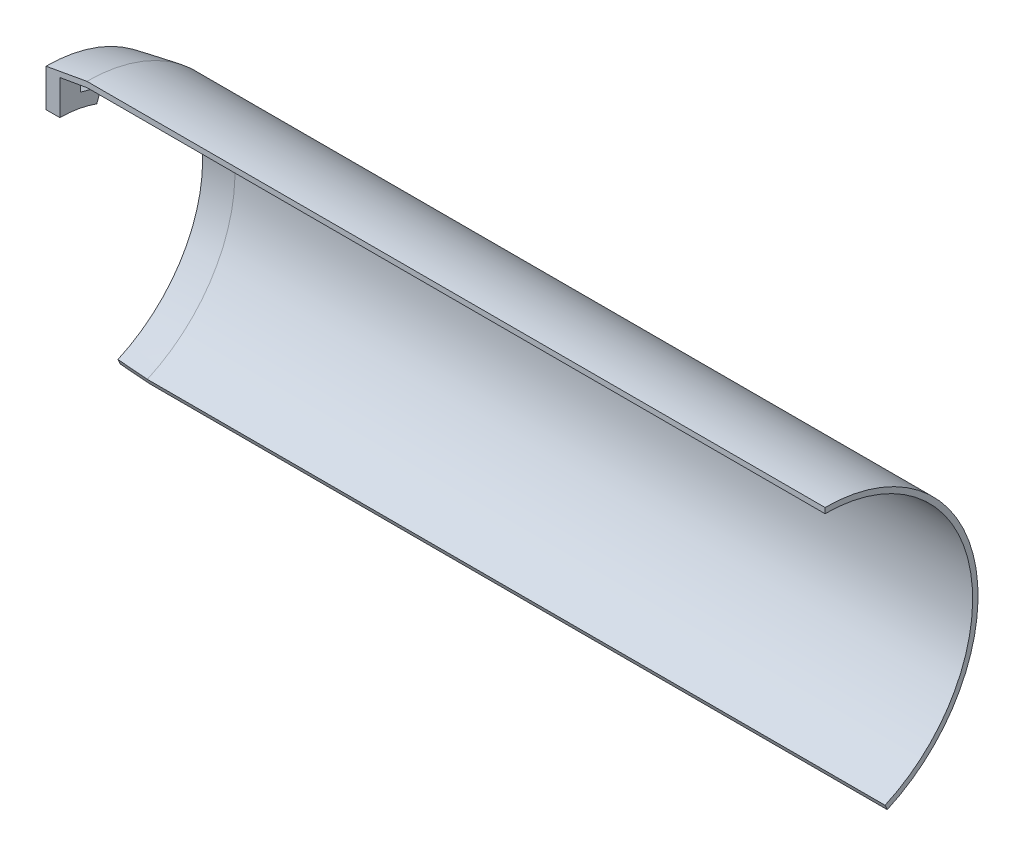
SolidWorks part; units mm, degrees
ref_plane "Front Plane" through (0, 0, 0) normal (0, 0, 1) x (1, 0, 0)
ref_plane "Top Plane" through (0, 0, 0) normal (0, 1, 0) x (1, 0, 0)
ref_plane "Right Plane" through (0, 0, 0) normal (1, 0, 0) x (0, 0, -1)
curve "Curve1"
  spline degree 3 poles (0, 0, 0) (-0.0123, 3.8916, 0) (-0.0274, 8.685, 0) (0.3616, 14.0857, 0) (0.5761, 16.0905, 0) (0.7825, 17.6048, 0) (0.9862, 18.8543, 0) (1.1887, 19.9315, 0) (1.3904, 20.8857, 0) (1.5917, 21.7465, 0) (1.7927, 22.5337, 0) (1.9935, 23.2611, 0) (2.1942, 23.9386, 0) (2.3947, 24.5739, 0) (2.5952, 25.1728, 0) (2.7956, 25.7401, 0) (2.9959, 26.2796, 0) (3.1962, 26.7943, 0) (3.3965, 27.2868, 0) (3.5967, 27.7594, 0) (3.7969, 28.2139, 0) (3.9971, 28.6519, 0) (4.1973, 29.0748, 0) (4.3974, 29.4838, 0) (4.5976, 29.8799, 0) (4.7977, 30.2641, 0) (4.9978, 30.6373, 0) (5.1979, 31.0001, 0) (5.398, 31.3533, 0) (5.5981, 31.6974, 0) (5.7982, 32.033, 0) (5.9983, 32.3606, 0) (6.1984, 32.6807, 0) (6.3985, 32.9935, 0) (6.5985, 33.2996, 0) (6.7986, 33.5993, 0) (6.9986, 33.8929, 0) (7.1987, 34.1806, 0) (7.3987, 34.4628, 0) (7.5988, 34.7397, 0) (7.7988, 35.0115, 0) (7.9989, 35.2785, 0) (8.1989, 35.5408, 0) (8.399, 35.7988, 0) (8.599, 36.0524, 0) (8.799, 36.3019, 0) (8.9991, 36.5476, 0) (9.1991, 36.7894, 0) (9.3991, 37.0275, 0) (9.5992, 37.2622, 0) (9.7992, 37.4934, 0) (9.9992, 37.7214, 0) (10.1992, 37.9461, 0) (10.3993, 38.1679, 0) (10.5993, 38.3866, 0) (10.7993, 38.6025, 0) (10.9993, 38.8156, 0) (11.1993, 39.026, 0) (11.3994, 39.2338, 0) (11.5994, 39.4391, 0) (11.7994, 39.6419, 0) (11.9994, 39.8422, 0) (12.1994, 40.0403, 0) (12.3995, 40.2361, 0) (12.5995, 40.4297, 0) (12.7995, 40.6212, 0) (12.9995, 40.8106, 0) (13.1995, 40.998, 0) (13.3995, 41.1834, 0) (13.5995, 41.3668, 0) (13.7995, 41.5484, 0) (13.9996, 41.7281, 0) (14.1996, 41.9061, 0) (14.3996, 42.0823, 0) (14.5996, 42.2568, 0) (14.7996, 42.4296, 0) (14.9996, 42.6008, 0) (15.1996, 42.7705, 0) (15.3996, 42.9385, 0) (15.5996, 43.1051, 0) (15.7996, 43.2701, 0) (15.9997, 43.4337, 0) (16.1997, 43.5959, 0) (16.3997, 43.7567, 0) (16.5997, 43.9161, 0) (16.7997, 44.0742, 0) (16.9997, 44.2309, 0) (17.1997, 44.3864, 0) (17.3997, 44.5406, 0) (17.5997, 44.6936, 0) (17.7997, 44.8453, 0) (17.9997, 44.9959, 0) (18.1997, 45.1453, 0) (18.3997, 45.2936, 0) (18.5997, 45.4407, 0) (18.7997, 45.5868, 0) (18.9997, 45.7317, 0) (19.1998, 45.8756, 0) (19.3998, 46.0185, 0) (19.5998, 46.1603, 0) (19.7998, 46.3011, 0) (19.9998, 46.4409, 0) (20.1998, 46.5797, 0) (20.3998, 46.7176, 0) (20.5998, 46.8546, 0) (20.7998, 46.9906, 0) (20.9998, 47.1257, 0) (21.1998, 47.2599, 0) (21.3998, 47.3932, 0) (21.5998, 47.5256, 0) (21.7998, 47.6572, 0) (21.9998, 47.788, 0) (22.1998, 47.9179, 0) (22.3998, 48.047, 0) (22.5998, 48.1753, 0) (22.7998, 48.3028, 0) (22.9998, 48.4295, 0) (23.1998, 48.5555, 0) (23.3998, 48.6807, 0) (23.5998, 48.8051, 0) (23.7998, 48.9288, 0) (23.9998, 49.0518, 0) (24.1998, 49.1741, 0) (24.3998, 49.2957, 0) (24.5998, 49.4165, 0) (24.7999, 49.5367, 0) (24.9999, 49.6562, 0) (25.1999, 49.7751, 0) (25.3999, 49.8933, 0) (25.5999, 50.0108, 0) (25.7999, 50.1277, 0) (25.9999, 50.2439, 0) (26.1999, 50.3596, 0) (26.3999, 50.4746, 0) (26.5999, 50.589, 0) (26.7999, 50.7028, 0) (26.9999, 50.8161, 0) (27.1999, 50.9287, 0) (27.3999, 51.0407, 0) (27.5999, 51.1522, 0) (27.7999, 51.2631, 0) (27.9999, 51.3735, 0) (28.1999, 51.4833, 0) (28.3999, 51.5926, 0) (28.5999, 51.7013, 0) (28.7999, 51.8095, 0) (28.9999, 51.9172, 0) (29.1999, 52.0243, 0) (29.3999, 52.131, 0) (29.5999, 52.2371, 0) (29.7999, 52.3428, 0) (29.9999, 52.4479, 0) (30.1999, 52.5526, 0) (30.3999, 52.6567, 0) (30.5999, 52.7604, 0) (30.7999, 52.8636, 0) (30.9999, 52.9664, 0) (31.1999, 53.0687, 0) (31.3999, 53.1705, 0) (31.5999, 53.2719, 0) (31.7999, 53.3728, 0) (31.9999, 53.4733, 0) (32.1999, 53.5733, 0) (32.3999, 53.6729, 0) (32.5999, 53.7721, 0) (32.7999, 53.8709, 0) (32.9999, 53.9692, 0) (33.1999, 54.0671, 0) (33.3999, 54.1646, 0) (33.5999, 54.2617, 0) (33.7999, 54.3584, 0) (33.9999, 54.4547, 0) (34.1999, 54.5506, 0) (34.3999, 54.6461, 0) (34.5999, 54.7412, 0) (34.7999, 54.836, 0) (34.9999, 54.9303, 0) (35.1999, 55.0243, 0) (35.3999, 55.1179, 0) (35.5999, 55.2111, 0) (35.7999, 55.304, 0) (35.9999, 55.3965, 0) (36.1999, 55.4887, 0) (36.3999, 55.5805, 0) (36.5999, 55.6719, 0) (36.7999, 55.763, 0) (36.9999, 55.8537, 0) (37.1999, 55.9441, 0) (37.3999, 56.0342, 0) (37.5999, 56.1239, 0) (37.7999, 56.2133, 0) (37.9999, 56.3024, 0) (38.1999, 56.3911, 0) (38.3999, 56.4795, 0) (38.5999, 56.5676, 0) (38.7999, 56.6554, 0) (38.9999, 56.7428, 0) (39.1999, 56.83, 0) (39.3999, 56.9168, 0) (39.5999, 57.0033, 0) (39.7999, 57.0896, 0) (39.9999, 57.1755, 0) (40.1999, 57.2611, 0) (40.3999, 57.3464, 0) (40.5999, 57.4314, 0) (40.7999, 57.5161, 0) (40.9999, 57.6006, 0) (41.1999, 57.6847, 0) (41.3999, 57.7686, 0) (41.6, 57.8522, 0) (41.8, 57.9355, 0) (42, 58.0185, 0) (42.2, 58.1012, 0) (42.4, 58.1837, 0) (42.6, 58.2659, 0) (42.8, 58.3479, 0) (43, 58.4295, 0) (43.2, 58.5109, 0) (43.4, 58.592, 0) (43.6, 58.6729, 0) (43.8, 58.7535, 0) (44, 58.8339, 0) (44.2, 58.914, 0) (44.4, 58.9938, 0) (44.6, 59.0734, 0) (44.8, 59.1528, 0) (45, 59.2319, 0) (45.2, 59.3107, 0) (45.4, 59.3893, 0) (45.6, 59.4677, 0) (45.8, 59.5458, 0) (46, 59.6237, 0) (46.2, 59.7014, 0) (46.4, 59.7788, 0) (46.6, 59.856, 0) (46.8, 59.9329, 0) (47, 60.0096, 0) (47.2, 60.0861, 0) (47.4, 60.1624, 0) (47.6, 60.2385, 0) (47.8, 60.3143, 0) (48, 60.3899, 0) (48.2, 60.4652, 0) (48.4, 60.5404, 0) (48.6, 60.6153, 0) (48.8, 60.6901, 0) (49, 60.7646, 0) (49.2, 60.8389, 0) (49.4, 60.913, 0) (49.6, 60.9869, 0) (49.8, 61.0605, 0) (50, 61.134, 0) (50.2, 61.2072, 0) (50.4, 61.2803, 0) (50.6, 61.3531, 0) (50.8, 61.4258, 0) (51, 61.4982, 0) (51.2, 61.5705, 0) (51.4, 61.6426, 0) (51.6, 61.7144, 0) (51.8, 61.7861, 0) (52, 61.8575, 0) (52.2, 61.9288, 0) (52.4, 61.9999, 0) (52.6, 62.0708, 0) (52.8, 62.1415, 0) (53, 62.212, 0) (53.2, 62.2824, 0) (53.4, 62.3525, 0) (53.6, 62.4225, 0) (53.8, 62.4923, 0) (54, 62.5619, 0) (54.2, 62.6313, 0) (54.4, 62.7006, 0) (54.6, 62.7696, 0) (54.8, 62.8385, 0) (55, 62.9072, 0) (55.2, 62.9758, 0) (55.4, 63.0441, 0) (55.6, 63.1123, 0) (55.8, 63.1803, 0) (56, 63.2482, 0) (56.2, 63.3159, 0) (56.4, 63.3834, 0) (56.6, 63.4507, 0) (56.8, 63.5179, 0) (57, 63.5849, 0) (57.2, 63.6518, 0) (57.4, 63.7185, 0) (57.6, 63.785, 0) (57.8, 63.8513, 0) (58, 63.9175, 0) (58.2, 63.9836, 0) (58.4, 64.0495, 0) (58.6, 64.1152, 0) (58.8, 64.1808, 0) (59, 64.2462, 0) (59.2, 64.3114, 0) (59.4, 64.3765, 0) (59.6, 64.4415, 0) (59.8, 64.5063, 0) (60, 64.5709, 0) (60.2, 64.6354, 0) (60.4, 64.6998, 0) (60.6, 64.764, 0) (60.8, 64.828, 0) (61, 64.8919, 0) (61.2, 64.9557, 0) (61.4, 65.0193, 0) (61.6, 65.0827, 0) (61.8, 65.1461, 0) (62, 65.2092, 0) (62.2, 65.2723, 0) (62.4, 65.3352, 0) (62.6, 65.3979, 0) (62.8, 65.4605, 0) (63, 65.523, 0) (63.2, 65.5853, 0) (63.4, 65.6475, 0) (63.6, 65.7096, 0) (63.8, 65.7715, 0) (64, 65.8333, 0) (64.2, 65.895, 0) (64.4, 65.9565, 0) (64.6, 66.0179, 0) (64.8, 66.0791, 0) (65, 66.1402, 0) (65.2, 66.2012, 0) (65.4, 66.2621, 0) (65.6, 66.3228, 0) (65.8, 66.3834, 0) (66, 66.4439, 0) (66.2, 66.5042, 0) (66.4, 66.5644, 0) (66.6, 66.6245, 0) (66.8, 66.6845, 0) (67, 66.7443, 0) (67.2, 66.804, 0) (67.4, 66.8636, 0) (67.6, 66.923, 0) (67.8, 66.9824, 0) (68, 67.0416, 0) (68.2, 67.1007, 0) (68.4, 67.1597, 0) (68.6, 67.2185, 0) (68.8, 67.2772, 0) (69, 67.3359, 0) (69.2, 67.3943, 0) (69.4, 67.4527, 0) (69.6, 67.511, 0) (69.8, 67.5691, 0) (70, 67.6271, 0) (70.2, 67.6851, 0) (70.4, 67.7428, 0) (70.6, 67.8005, 0) (70.8, 67.8581, 0) (71, 67.9155, 0) (71.2, 67.9729, 0) (71.4, 68.0301, 0) (71.6, 68.0872, 0) (71.8, 68.1442, 0) (72, 68.2011, 0) (72.2, 68.2579, 0) (72.4, 68.3145, 0) (72.6, 68.3711, 0) (72.8, 68.4276, 0) (73, 68.4839, 0) (73.2, 68.5401, 0) (73.4, 68.5963, 0) (73.6, 68.6523, 0) (73.8, 68.7082, 0) (74, 68.764, 0) (74.2, 68.8197, 0) (74.4, 68.8753, 0) (74.6, 68.9308, 0) (74.8, 68.9862, 0) (75, 69.0415, 0) (75.2, 69.0966, 0) (75.4, 69.1517, 0) (75.6, 69.2067, 0) (75.8, 69.2616, 0) (76, 69.3164, 0) (76.2, 69.371, 0) (76.4, 69.4256, 0) (76.6, 69.4801, 0) (76.8, 69.5344, 0) (77, 69.5887, 0) (77.2, 69.6429, 0) (77.4, 69.697, 0) (77.6, 69.751, 0) (77.8, 69.8048, 0) (78, 69.8586, 0) (78.2, 69.9123, 0) (78.4, 69.9659, 0) (78.6, 70.0194, 0) (78.8, 70.0728, 0) (79, 70.1261, 0) (79.2, 70.1793, 0) (79.4, 70.2324, 0) (79.6, 70.2855, 0) (79.8, 70.3384, 0) (80, 70.3912, 0) (80.2, 70.444, 0) (80.4, 70.4966, 0) (80.6, 70.5492, 0) (80.8, 70.6017, 0) (81, 70.6541, 0) (81.2, 70.7064, 0) (81.4, 70.7586, 0) (81.6, 70.8107, 0) (81.8, 70.8627, 0) (82, 70.9146, 0) (82.2, 70.9665, 0) (82.4, 71.0182, 0) (82.6, 71.0699, 0) (82.8, 71.1215, 0) (83, 71.173, 0) (83.2, 71.2244, 0) (83.4, 71.2757, 0) (83.6, 71.3269, 0) (83.8, 71.3781, 0) (84, 71.4291, 0) (84.2, 71.4801, 0) (84.4, 71.531, 0) (84.6, 71.5818, 0) (84.8, 71.6325, 0) (85, 71.6832, 0) (85.2, 71.7337, 0) (85.4, 71.7842, 0) (85.6, 71.8346, 0) (85.8, 71.8849, 0) (86, 71.9351, 0) (86.2, 71.9853, 0) (86.4, 72.0354, 0) (86.6, 72.0853, 0) (86.8, 72.1352, 0) (87, 72.1851, 0) (87.2, 72.2348, 0) (87.4, 72.2845, 0) (87.6, 72.3341, 0) (87.8, 72.3836, 0) (88, 72.433, 0) (88.2, 72.4823, 0) (88.4, 72.5316, 0) (88.6, 72.5808, 0) (88.8, 72.6299, 0) (89, 72.6789, 0) (89.2, 72.7279, 0) (89.4, 72.7768, 0) (89.6, 72.8256, 0) (89.8, 72.8743, 0) (90, 72.923, 0) (90.2, 72.9716, 0) (90.4, 73.0201, 0) (90.6, 73.0685, 0) (90.8, 73.1168, 0) (91, 73.1651, 0) (91.2, 73.2133, 0) (91.4, 73.2614, 0) (91.6, 73.3095, 0) (91.8, 73.3575, 0) (92, 73.4054, 0) (92.2, 73.4532, 0) (92.4, 73.501, 0) (92.6, 73.5487, 0) (92.8, 73.5963, 0) (93, 73.6439, 0) (93.2, 73.6913, 0) (93.4, 73.7387, 0) (93.6, 73.7861, 0) (93.8, 73.8333, 0) (94, 73.8805, 0) (94.2, 73.9276, 0) (94.4, 73.9747, 0) (94.6, 74.0217, 0) (94.8, 74.0686, 0) (95, 74.1154, 0) (95.2, 74.1622, 0) (95.4, 74.2089, 0) (95.6, 74.2556, 0) (95.8, 74.3021, 0) (96, 74.3486, 0) (96.2, 74.3951, 0) (96.4, 74.4414, 0) (96.6, 74.4877, 0) (96.8, 74.534, 0) (97, 74.5801, 0) (97.2, 74.6262, 0) (97.4, 74.6723, 0) (97.6, 74.7182, 0) (97.8, 74.7641, 0) (98, 74.81, 0) (98.2, 74.8557, 0) (98.4, 74.9014, 0) (98.6, 74.9471, 0) (98.8, 74.9926, 0) (99, 75.0382, 0) (99.2, 75.0836, 0) (99.4, 75.129, 0) (99.6, 75.1743, 0) (99.8, 75.2196, 0) (100, 75.2647, 0) (100.2, 75.3099, 0) (100.4, 75.3549, 0) (100.6, 75.3999, 0) (100.8, 75.4449, 0) (101, 75.4898, 0) (101.2, 75.5346, 0) (101.4, 75.5793, 0) (101.6, 75.624, 0) (101.8, 75.6686, 0) (102, 75.7132, 0) (102.2, 75.7577, 0) (102.4, 75.8022, 0) (102.6, 75.8465, 0) (102.8, 75.8909, 0) (103, 75.9351, 0) (103.2, 75.9793, 0) (103.4, 76.0235, 0) (103.6, 76.0676, 0) (103.8, 76.1116, 0) (104, 76.1556, 0) (104.2, 76.1995, 0) (104.4, 76.2433, 0) (104.6, 76.2871, 0) (104.8, 76.3308, 0) (105, 76.3745, 0) (105.2, 76.4181, 0) (105.4, 76.4617, 0) (105.6, 76.5052, 0) (105.8, 76.5486, 0) (106, 76.592, 0) (106.2, 76.6353, 0) (106.4, 76.6786, 0) (106.6, 76.7218, 0) (106.8, 76.7649, 0) (107, 76.808, 0) (107.2, 76.8511, 0) (107.4, 76.8941, 0) (107.6, 76.937, 0) (107.8, 76.9799, 0) (108, 77.0227, 0) (108.2, 77.0655, 0) (108.4, 77.1082, 0) (108.6, 77.1508, 0) (108.8, 77.1934, 0) (109, 77.236, 0) (109.2, 77.2784, 0) (109.4, 77.3209, 0) (109.6, 77.3633, 0) (109.8, 77.4056, 0) (110, 77.4479, 0) (110.2, 77.4901, 0) (110.4, 77.5322, 0) (110.6, 77.5743, 0) (110.8, 77.6164, 0) (111, 77.6584, 0) (111.2, 77.7004, 0) (111.4, 77.7423, 0) (111.6, 77.7841, 0) (111.8, 77.8259, 0) (112, 77.8676, 0) (112.2, 77.9093, 0) (112.4, 77.951, 0) (112.6, 77.9925, 0) (112.8, 78.0341, 0) (113, 78.0756, 0) (113.2, 78.117, 0) (113.4, 78.1584, 0) (113.6, 78.1997, 0) (113.8, 78.241, 0) (114, 78.2822, 0) (114.2, 78.3234, 0) (114.4, 78.3645, 0) (114.6, 78.4056, 0) (114.8, 78.4466, 0) (115, 78.4876, 0) (115.2, 78.5285, 0) (115.4, 78.5694, 0) (115.6, 78.6102, 0) (115.8, 78.651, 0) (116, 78.6917, 0) (116.2, 78.7324, 0) (116.4, 78.773, 0) (116.6, 78.8136, 0) (116.8, 78.8541, 0) (117, 78.8946, 0) (117.2, 78.935, 0) (117.4, 78.9754, 0) (117.6, 79.0158, 0) (117.8, 79.0561, 0) (118, 79.0963, 0) (118.2, 79.1365, 0) (118.4, 79.1766, 0) (118.6, 79.2167, 0) (118.8, 79.2568, 0) (119, 79.2968, 0) (119.2, 79.3368, 0) (119.4, 79.3767, 0) (119.6, 79.4165, 0) (119.8, 79.4564, 0) (120, 79.4961, 0) (120.2, 79.5358, 0) (120.4, 79.5755, 0) (120.6, 79.6152, 0) (120.8, 79.6547, 0) (121, 79.6943, 0) (121.2, 79.7338, 0) (121.4, 79.7732, 0) (121.6, 79.8126, 0) (121.8, 79.852, 0) (122, 79.8913, 0) (122.2, 79.9306, 0) (122.4, 79.9698, 0) (122.6, 80.009, 0) (122.8, 80.0481, 0) (123, 80.0872, 0) (123.2, 80.1262, 0) (123.4, 80.1652, 0) (123.6, 80.2042, 0) (123.8, 80.2431, 0) (124, 80.282, 0) (124.2, 80.3208, 0) (124.4, 80.3596, 0) (124.6, 80.3983, 0) (124.8, 80.437, 0) (125, 80.4757, 0) (125.2, 80.5143, 0) (125.4, 80.5528, 0) (125.6, 80.5914, 0) (125.8, 80.6298, 0) (126, 80.6683, 0) (126.2, 80.7067, 0) (126.4, 80.745, 0) (126.6, 80.7833, 0) (126.8, 80.8216, 0) (127, 80.8598, 0) (127.2, 80.898, 0) (127.4, 80.9361, 0) (127.6, 80.9742, 0) (127.8, 81.0123, 0) (128, 81.0503, 0) (128.2, 81.0883, 0) (128.4, 81.1262, 0) (128.6, 81.1641, 0) (128.8, 81.2019, 0) (129, 81.2397, 0) (129.2, 81.2775, 0) (129.4, 81.3152, 0) (129.6, 81.3529, 0) (129.8, 81.3906, 0) (130, 81.4282, 0) (130.2, 81.4657, 0) (130.4, 81.5032, 0) (130.6, 81.5407, 0) (130.8, 81.5782, 0) (131, 81.6156, 0) (131.2, 81.6529, 0) (131.4, 81.6902, 0) (131.6, 81.7275, 0) (131.8, 81.7648, 0) (132, 81.802, 0) (132.2, 81.8391, 0) (132.4, 81.8763, 0) (132.6, 81.9133, 0) (132.8, 81.9504, 0) (133, 81.9874, 0) (133.2, 82.0244, 0) (133.4, 82.0613, 0) (133.6, 82.0982, 0) (133.8, 82.135, 0) (134, 82.1718, 0) (134.2, 82.2086, 0) (134.4, 82.2454, 0) (134.6, 82.282, 0) (134.8, 82.3187, 0) (135, 82.3553, 0) (135.2, 82.3919, 0) (135.4, 82.4285, 0) (135.6, 82.465, 0) (135.8, 82.5014, 0) (136, 82.5379, 0) (136.2, 82.5743, 0) (136.4, 82.6106, 0) (136.6, 82.6469, 0) (136.8, 82.6832, 0) (137, 82.7195, 0) (137.2, 82.7557, 0) (137.4, 82.7919, 0) (137.6, 82.828, 0) (137.8, 82.8641, 0) (138, 82.9001, 0) (138.2, 82.9362, 0) (138.4, 82.9722, 0) (138.6, 83.0081, 0) (138.8, 83.044, 0) (139, 83.0799, 0) (139.2, 83.1158, 0) (139.4, 83.1516, 0) (139.6, 83.1873, 0) (139.8, 83.2231, 0) (140, 83.2588, 0) (140.2, 83.2944, 0) (140.4, 83.3301, 0) (140.6, 83.3657, 0) (140.8, 83.4012, 0) (141, 83.4367, 0) (141.2, 83.4722, 0) (141.4, 83.5077, 0) (141.6, 83.5431, 0) (141.8, 83.5785, 0) (142, 83.6138, 0) (142.2, 83.6491, 0) (142.4, 83.6844, 0) (142.6, 83.7197, 0) (142.8, 83.7549, 0) (143, 83.79, 0) (143.2, 83.8252, 0) (143.4, 83.8603, 0) (143.6, 83.8954, 0) (143.8, 83.9304, 0) (144, 83.9654, 0) (144.2, 84.0004, 0) (144.4, 84.0353, 0) (144.6, 84.0702, 0) (144.8, 84.1051, 0) (145, 84.1399, 0) (145.2, 84.1747, 0) (145.4, 84.2095, 0) (145.6, 84.2442, 0) (145.8, 84.2789, 0) (146, 84.3136, 0) (146.2, 84.3482, 0) (146.4, 84.3828, 0) (146.6, 84.4174, 0) (146.8, 84.4519, 0) (147, 84.4864, 0) (147.2, 84.5209, 0) (147.4, 84.5553, 0) (147.6, 84.5897, 0) (147.8, 84.6241, 0) (148, 84.6584, 0) (148.2, 84.6927, 0) (148.4, 84.727, 0) (148.6, 84.7612, 0) (148.8, 84.7954, 0) (149, 84.8296, 0) (149.2, 84.8638, 0) (149.4, 84.8979, 0) (149.6, 84.9319, 0) (149.8, 84.966, 0) (149.9333, 84.9887, 0) (150, 85, 0) knots 0 0 0 0 0.061462 0.075706 0.085548 0.093322 0.099856 0.105554 0.110643 0.115268 0.119525 0.123482 0.127192 0.130691 0.13401 0.137173 0.140199 0.143104 0.145901 0.148602 0.151215 0.15375 0.156213 0.158609 0.160946 0.163227 0.165456 0.167638 0.169775 0.171871 0.173928 0.17595 0.177937 0.179893 0.181819 0.183716 0.185587 0.187433 0.189255 0.191054 0.192831 0.194589 0.196326 0.198045 0.199747 0.201431 0.2031 0.204753 0.206391 0.208015 0.209626 0.211223 0.212808 0.214381 0.215942 0.217493 0.219032 0.220561 0.22208 0.22359 0.225091 0.226582 0.228065 0.229539 0.231006 0.232464 0.233915 0.235359 0.236795 0.238225 0.239648 0.241065 0.242475 0.243879 0.245277 0.24667 0.248057 0.249438 0.250814 0.252185 0.253551 0.254913 0.256269 0.257621 0.258968 0.260311 0.26165 0.262984 0.264315 0.265641 0.266964 0.268282 0.269598 0.270909 0.272217 0.273522 0.274823 0.276121 0.277416 0.278707 0.279996 0.281281 0.282564 0.283843 0.28512 0.286394 0.287666 0.288935 0.290201 0.291465 0.292726 0.293985 0.295241 0.296495 0.297747 0.298996 0.300243 0.301489 0.302732 0.303972 0.305211 0.306448 0.307683 0.308916 0.310147 0.311376 0.312604 0.313829 0.315053 0.316275 0.317495 0.318714 0.319931 0.321147 0.32236 0.323573 0.324783 0.325993 0.3272 0.328406 0.329611 0.330815 0.332017 0.333217 0.334416 0.335614 0.336811 0.338006 0.3392 0.340393 0.341584 0.342775 0.343964 0.345152 0.346339 0.347524 0.348709 0.349892 0.351074 0.352256 0.353436 0.354615 0.355793 0.35697 0.358146 0.359321 0.360495 0.361668 0.36284 0.364011 0.365182 0.366351 0.36752 0.368687 0.369854 0.37102 0.372185 0.373349 0.374512 0.375674 0.376836 0.377997 0.379157 0.380316 0.381475 0.382632 0.383789 0.384946 0.386101 0.387256 0.38841 0.389563 0.390716 0.391868 0.393019 0.39417 0.39532 0.396469 0.397618 0.398766 0.399913 0.40106 0.402206 0.403351 0.404496 0.40564 0.406784 0.407927 0.409069 0.410211 0.411353 0.412493 0.413633 0.414773 0.415912 0.417051 0.418189 0.419326 0.420463 0.4216 0.422736 0.423871 0.425006 0.426141 0.427275 0.428408 0.429541 0.430674 0.431806 0.432937 0.434068 0.435199 0.436329 0.437459 0.438588 0.439717 0.440846 0.441974 0.443101 0.444229 0.445355 0.446482 0.447608 0.448733 0.449858 0.450983 0.452107 0.453231 0.454355 0.455478 0.456601 0.457723 0.458845 0.459967 0.461088 0.462209 0.46333 0.46445 0.46557 0.46669 0.467809 0.468928 0.470046 0.471164 0.472282 0.4734 0.474517 0.475634 0.47675 0.477866 0.478982 0.480098 0.481213 0.482328 0.483443 0.484557 0.485671 0.486785 0.487898 0.489011 0.490124 0.491237 0.492349 0.493461 0.494573 0.495684 0.496796 0.497906 0.499017 0.500127 0.501237 0.502347 0.503457 0.504566 0.505675 0.506784 0.507892 0.509001 0.510109 0.511216 0.512324 0.513431 0.514538 0.515645 0.516752 0.517858 0.518964 0.52007 0.521175 0.522281 0.523386 0.524491 0.525595 0.5267 0.527804 0.528908 0.530012 0.531116 0.532219 0.533322 0.534425 0.535528 0.53663 0.537733 0.538835 0.539937 0.541038 0.54214 0.543241 0.544342 0.545443 0.546544 0.547644 0.548745 0.549845 0.550945 0.552044 0.553144 0.554243 0.555342 0.556441 0.55754 0.558639 0.559737 0.560836 0.561934 0.563032 0.564129 0.565227 0.566324 0.567421 0.568518 0.569615 0.570712 0.571809 0.572905 0.574001 0.575097 0.576193 0.577289 0.578384 0.57948 0.580575 0.58167 0.582765 0.58386 0.584954 0.586049 0.587143 0.588237 0.589331 0.590425 0.591519 0.592612 0.593706 0.594799 0.595892 0.596985 0.598078 0.59917 0.600263 0.601355 0.602448 0.60354 0.604632 0.605724 0.606815 0.607907 0.608998 0.61009 0.611181 0.612272 0.613363 0.614453 0.615544 0.616635 0.617725 0.618815 0.619905 0.620995 0.622085 0.623175 0.624265 0.625354 0.626443 0.627533 0.628622 0.629711 0.6308 0.631888 0.632977 0.634066 0.635154 0.636242 0.637331 0.638419 0.639507 0.640594 0.641682 0.64277 0.643857 0.644945 0.646032 0.647119 0.648206 0.649293 0.65038 0.651467 0.652553 0.65364 0.654726 0.655813 0.656899 0.657985 0.659071 0.660157 0.661243 0.662328 0.663414 0.664499 0.665585 0.66667 0.667755 0.66884 0.669925 0.67101 0.672095 0.67318 0.674264 0.675349 0.676433 0.677518 0.678602 0.679686 0.68077 0.681854 0.682938 0.684022 0.685105 0.686189 0.687272 0.688356 0.689439 0.690522 0.691605 0.692688 0.693771 0.694854 0.695937 0.69702 0.698102 0.699185 0.700267 0.70135 0.702432 0.703514 0.704596 0.705678 0.70676 0.707842 0.708924 0.710006 0.711087 0.712169 0.71325 0.714332 0.715413 0.716494 0.717575 0.718656 0.719737 0.720818 0.721899 0.72298 0.724061 0.725141 0.726222 0.727302 0.728382 0.729463 0.730543 0.731623 0.732703 0.733783 0.734863 0.735943 0.737023 0.738103 0.739182 0.740262 0.741341 0.742421 0.7435 0.744579 0.745659 0.746738 0.747817 0.748896 0.749975 0.751054 0.752133 0.753211 0.75429 0.755369 0.756447 0.757526 0.758604 0.759682 0.760761 0.761839 0.762917 0.763995 0.765073 0.766151 0.767229 0.768307 0.769385 0.770462 0.77154 0.772618 0.773695 0.774773 0.77585 0.776927 0.778005 0.779082 0.780159 0.781236 0.782313 0.78339 0.784467 0.785544 0.786621 0.787698 0.788774 0.789851 0.790928 0.792004 0.793081 0.794157 0.795233 0.79631 0.797386 0.798462 0.799538 0.800614 0.80169 0.802766 0.803842 0.804918 0.805994 0.80707 0.808145 0.809221 0.810296 0.811372 0.812447 0.813523 0.814598 0.815674 0.816749 0.817824 0.818899 0.819974 0.821049 0.822124 0.823199 0.824274 0.825349 0.826424 0.827499 0.828573 0.829648 0.830723 0.831797 0.832872 0.833946 0.835021 0.836095 0.837169 0.838244 0.839318 0.840392 0.841466 0.84254 0.843614 0.844688 0.845762 0.846836 0.84791 0.848984 0.850058 0.851131 0.852205 0.853279 0.854352 0.855426 0.856499 0.857573 0.858646 0.859719 0.860793 0.861866 0.862939 0.864012 0.865085 0.866159 0.867232 0.868305 0.869378 0.87045 0.871523 0.872596 0.873669 0.874742 0.875814 0.876887 0.87796 0.879032 0.880105 0.881177 0.88225 0.883322 0.884395 0.885467 0.886539 0.887611 0.888684 0.889756 0.890828 0.8919 0.892972 0.894044 0.895116 0.896188 0.89726 0.898332 0.899404 0.900475 0.901547 0.902619 0.90369 0.904762 0.905834 0.906905 0.907977 0.909048 0.91012 0.911191 0.912262 0.913334 0.914405 0.915476 0.916548 0.917619 0.91869 0.919761 0.920832 0.921903 0.922974 0.924045 0.925116 0.926187 0.927258 0.928329 0.929399 0.93047 0.931541 0.932612 0.933682 0.934753 0.935823 0.936894 0.937965 0.939035 0.940105 0.941176 0.942246 0.943317 0.944387 0.945457 0.946527 0.947598 0.948668 0.949738 0.950808 0.951878 0.952948 0.954018 0.955088 0.956158 0.957228 0.958298 0.959368 0.960438 0.961508 0.962577 0.963647 0.964717 0.965786 0.966856 0.967926 0.968995 0.970065 0.971134 0.972204 0.973273 0.974343 0.975412 0.976481 0.977551 0.97862 0.979689 0.980759 0.981828 0.982897 0.983966 0.985035 0.986104 0.987173 0.988242 0.989311 0.99038 0.991449 0.992518 0.993587 0.994656 0.995725 0.996794 0.997863 0.998931 1 1 1 1
sketch "Sketch1" plane through (0, 0, 0) normal (0, 0, 1) x (1, 0, 0)
  line L0 (150, 85) -> (560, 85)
  line L1 (150.2533, 82) -> (560, 82)
  line L2 (560, 85) -> (560, 82)
  line L3 (0, 0) -> (3, 0)
  line L4 (3, 0.0095) -> (3, 0)
  line L5 (3, 0) -> (560, 0) construction
  line L6 (560, 0) -> (560, 82) construction
  line L7 (540, 75) -> (135, 75) construction
  line L8 (135, 75) -> (135, 0) construction
  line L9 (135, 75) -> (135, 79.3054) construction
  line L10 (135, 79.3054) -> (135, 78.3)
  line L11 (135, 78.3) -> (129.5999, 78.3)
  line L12 (135, 79.3054) -> (135, 60)
  line L13 (135, 60) -> (127.3, 60)
  line L14 (127.3, 60) -> (127.3, 80.9171)
  line L15 (135, 79.3054) -> (135, 82.3553)
  spline S0 degree 3 poles (-8986.9098, -41.7657) (268.2939, -268.0766) (-9.419, -121.7008) (0.3616, 14.0857) (0.5761, 16.0905) (0.7825, 17.6048) (0.9862, 18.8543) (1.1887, 19.9315) (1.3904, 20.8857) (1.5917, 21.7465) (1.7927, 22.5337) (1.9935, 23.2611) (2.2538, 24.14) (2.5806, 25.1462) (2.9836, 26.2595) (3.3859, 27.2713) (3.7877, 28.2016) (4.1891, 29.0648) (4.5903, 29.8717) (5.0533, 30.7478) (5.5832, 31.6835) (6.1854, 32.6697) (6.7872, 33.5906) (7.4515, 34.5461) (8.1828, 35.531) (8.9851, 36.54) (9.8503, 37.5625) (10.7826, 38.5957) (11.785, 39.6369) (12.851, 40.6804) (13.984, 41.7246) (15.1862, 42.7682) (16.388, 43.7553) (17.6544, 44.7435) (18.9876, 45.7315) (20.3892, 46.7179) (21.7905, 47.6579) (23.2571, 48.5984) (24.7904, 49.5382) (26.3916, 50.4762) (28.0583, 51.4122) (29.7917, 52.3451) (31.5927, 53.2742) (33.4594, 54.1996) (35.3929, 55.1207) (37.4597, 56.0672) (39.5933, 57.0066) (41.8602, 57.9666) (44.1937, 58.9175) (46.6606, 59.8853) (49.2604, 60.8677) (51.994, 61.8617) (54.861, 62.8656) (57.7946, 63.8556) (60.8615, 64.8536) (64.0615, 65.8584) (67.4615, 66.8882) (70.9951, 67.9202) (74.6621, 68.9539) (78.4621, 69.9886) (82.4622, 71.0404) (86.6623, 72.1071) (91.0624, 73.1864) (95.6625, 74.2764) (100.4626, 75.3753) (105.4628, 76.4816) (110.6629, 77.5938) (116.063, 78.7107) (121.6632, 79.8312) (127.5299, 80.9671) (133.6633, 82.1162) (140.0634, 83.2764) (145.1985, 84.1774) (148.3332, 84.7158) (149.3333, 84.8865) (149.6, 84.9319) (223.6179, 97.5333) (298.9359, 102.0891) (-1136.5614, 8986.8496) knots -2.065319 -2.065319 -2.065319 -2.065319 0.061462 0.075706 0.085548 0.093322 0.099856 0.105554 0.110643 0.115268 0.119525 0.123482 0.127192 0.13401 0.140199 0.145901 0.151215 0.156213 0.160946 0.165456 0.171871 0.177937 0.183716 0.189255 0.196326 0.2031 0.209626 0.217493 0.225091 0.232464 0.241065 0.249438 0.257621 0.265641 0.274823 0.283843 0.292726 0.301489 0.311376 0.321147 0.330815 0.341584 0.352256 0.36284 0.374512 0.386101 0.398766 0.411353 0.425006 0.438588 0.453231 0.468928 0.484557 0.501237 0.517858 0.535528 0.554243 0.574001 0.593706 0.614453 0.636242 0.659071 0.682938 0.707842 0.733783 0.760761 0.788774 0.817824 0.84791 0.879032 0.912262 0.946527 0.981828 0.994656 0.996794 0.997863 0.998931 2.183399 2.183399 2.183399 2.183399 only from (0, 0) to (150, 85) construction
  spline S1 degree 3 poles (0, 0) (-0.0123, 3.8916) (-0.0274, 8.685) (0.3616, 14.0857) (0.5761, 16.0905) (0.7825, 17.6048) (0.9862, 18.8543) (1.1887, 19.9315) (1.3904, 20.8857) (1.5917, 21.7465) (1.7927, 22.5337) (1.9935, 23.2611) (2.2538, 24.14) (2.5806, 25.1462) (2.9836, 26.2595) (3.3859, 27.2713) (3.7877, 28.2016) (4.1891, 29.0648) (4.5903, 29.8717) (5.0533, 30.7478) (5.5832, 31.6835) (6.1854, 32.6697) (6.7872, 33.5906) (7.4515, 34.5461) (8.1828, 35.531) (8.9851, 36.54) (9.8503, 37.5625) (10.7826, 38.5957) (11.785, 39.6369) (12.851, 40.6804) (13.984, 41.7246) (15.1862, 42.7682) (16.388, 43.7553) (17.6544, 44.7435) (18.9876, 45.7315) (20.3892, 46.7179) (21.7905, 47.6579) (23.2571, 48.5984) (24.7904, 49.5382) (26.3916, 50.4762) (28.0583, 51.4122) (29.7917, 52.3451) (31.5927, 53.2742) (33.4594, 54.1996) (35.3929, 55.1207) (37.4597, 56.0672) (39.5933, 57.0066) (41.8602, 57.9666) (44.1937, 58.9175) (46.6606, 59.8853) (49.2604, 60.8677) (51.994, 61.8617) (54.861, 62.8656) (57.7946, 63.8556) (60.8615, 64.8536) (64.0615, 65.8584) (67.4615, 66.8882) (70.9951, 67.9202) (74.6621, 68.9539) (78.4621, 69.9886) (82.4622, 71.0404) (86.6623, 72.1071) (91.0624, 73.1864) (95.6625, 74.2764) (100.4626, 75.3753) (105.4628, 76.4816) (110.6629, 77.5938) (116.063, 78.7107) (121.6632, 79.8312) (127.5299, 80.9671) (133.6633, 82.1162) (140.0634, 83.2764) (145.1985, 84.1774) (148.3332, 84.7158) (149.4, 84.8979) (149.7333, 84.9547) (149.9333, 84.9887) (150, 85) knots 0 0 0 0 0.061462 0.075706 0.085548 0.093322 0.099856 0.105554 0.110643 0.115268 0.119525 0.123482 0.127192 0.13401 0.140199 0.145901 0.151215 0.156213 0.160946 0.165456 0.171871 0.177937 0.183716 0.189255 0.196326 0.2031 0.209626 0.217493 0.225091 0.232464 0.241065 0.249438 0.257621 0.265641 0.274823 0.283843 0.292726 0.301489 0.311376 0.321147 0.330815 0.341584 0.352256 0.36284 0.374512 0.386101 0.398766 0.411353 0.425006 0.438588 0.453231 0.468928 0.484557 0.501237 0.517858 0.535528 0.554243 0.574001 0.593706 0.614453 0.636242 0.659071 0.682938 0.707842 0.733783 0.760761 0.788774 0.817824 0.84791 0.879032 0.912262 0.946527 0.981828 0.994656 0.996794 0.998931 1 1 1 1
  spline S4 degree 1 poles (3, 0.0095) (150.2533, 82) knots 0 0 1 1 construction
  spline S5 degree 3 poles (3, 0.0095) (2.9938, 1.9694) (2.982, 5.9112) (3.1447, 11.6915) (3.6709, 17.3262) (4.8192, 22.7297) (6.752, 27.816) (10.434, 34.0689) (16.886, 40.7698) (26.3115, 47.2193) (36.5885, 52.5329) (47.3393, 57.0416) (62.0527, 62.2707) (80.8898, 67.7174) (103.8027, 73.1709) (119.6464, 76.4013) (128.7004, 78.1304) (130.4993, 78.4702) (132.2991, 78.8064) (134.0994, 79.1404) (140.0771, 80.2374) (145.6154, 81.2107) (150.2533, 82) knots 0 0 0 0 0.031208 0.062417 0.093625 0.124833 0.156041 0.18725 0.249666 0.312083 0.374499 0.436916 0.499332 0.624165 0.748998 0.873334 0.880588 0.895097 0.902352 0.909606 0.924115 0.998664 0.998664 0.998664 0.998664
  dimension "D2" = 410
  dimension "D4" = 75
  dimension "D5" = 405
  dimension "D6" = 20
  dimension "D7" = 78.3
  dimension "D1" = 7.7
  dimension "D8" = 60
  dimension "D3" = 3
revolve "Revolve5" add sketch "Sketch1" angle 156 about L5 region at (347.3872, 83.4524, 0) reverse direction yes
revolve "Revolve6" add sketch "Sketch1<8>" angle 20 about L5 region at (131.1491, 80.1149, 0) region at (133.1956, 78.6359, 0) region at (131.161, 69.1178, 0) reverse direction yes
sketch "Sketch1<8>" plane through (0, 0, 0) normal (0, 0, 1) x (1, 0, 0) same geometry as "Sketch1"
ref_axis "Axis1" through (150, -77.6514, -34.5726) along (1, 0, 0)
ref_plane "Plane1" through (150.2533, 0, 0) normal (1, 0, 0) x (0, 0, -1)
revolve "Revolve7" add sketch "Sketch1<9>" angle 50 about L5 region at (131.1491, 80.1149, 0) reverse direction yes
sketch "Sketch1<9>" plane through (0, 0, 0) normal (0, 0, 1) x (1, 0, 0) same geometry as "Sketch1"
sketch "Sketch4" plane through (135, 0, 0) normal (-1, 0, 0) x (0, 0, 1)
  circle A0 centre (-34.5726, -77.6514) radius 134.7675
extrude "Cut-Extrude2" cut sketch "Sketch4" along normal blind 170
sketch "Sketch5" plane through (127.3, 0, 0) normal (-1, 0, 0) x (0, 0, 1)
  line L0 (-23.0864, 63.4293) -> (-11.4899, 66.5149)
  line L1 (-11.4899, 66.5149) -> (-11.4899, 74.1147)
  line L2 (-25.6515, 70.4769) -> (-23.0864, 63.4293)
  line L3 (0, 0) -> (0, 82) construction
  arc A0 (0, 60) -> (-20.5212, 56.3816) centre (0, 0) ccw construction
  arc A1 (0, 60) -> (-20.5212, 56.3816) centre (0, 0) ccw
  arc A2 (-11.4899, 74.1147) -> (-25.6515, 70.4769) centre (0, 0) ccw
  arc A3 (-11.4899, 66.5149) -> (-23.0864, 63.4293) centre (0, 0) ccw construction
  arc A4 (0, 75) -> (-25.6515, 70.4769) centre (0, 0) ccw construction
  arc A5 (0, 67.5) -> (-23.0864, 63.4293) centre (0, 0) ccw construction
  line M7 (-26.6307, 73.1671) -> (-20.5212, 56.3816)
  dimension "D3" = 12
  dimension "D1" = 15
  dimension "D2" = 7.5
extrude "Cut-Extrude3" cut sketch "Sketch5" against normal blind 10 contours L1 A2 L0 M7 region at (127.3, 68.8759, -17.9888)
